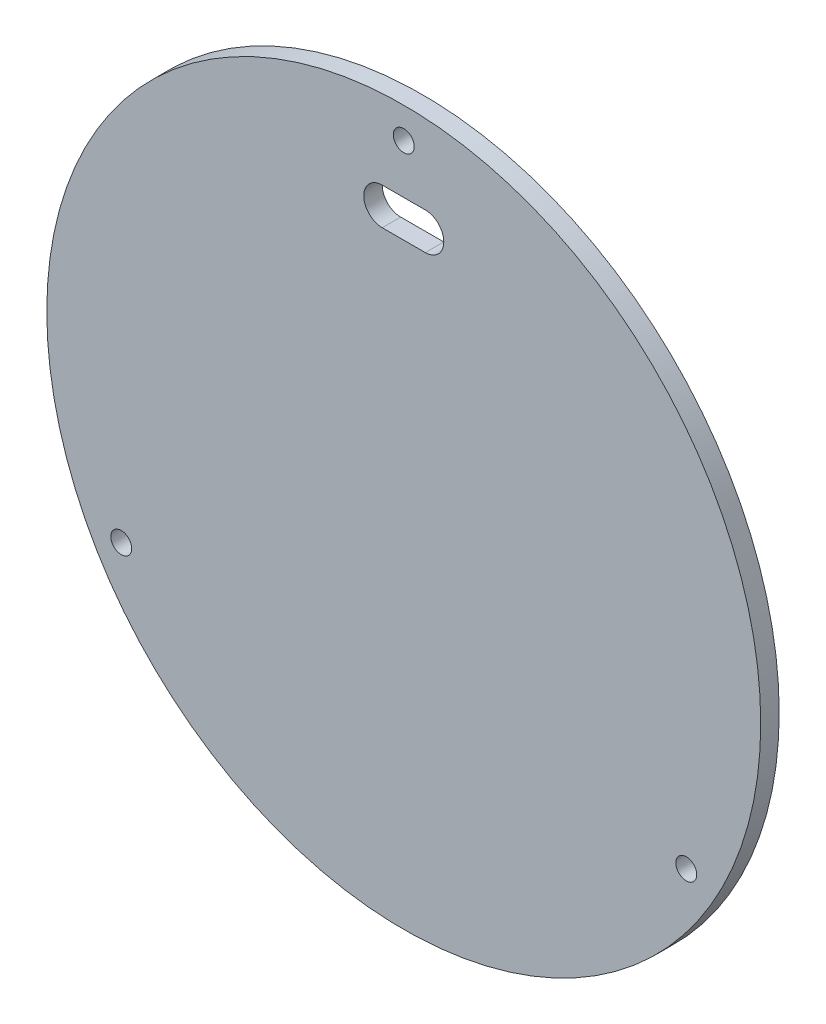
SolidWorks part; units mm, degrees
ref_plane "Front Plane" through (0, 0, 0) normal (0, 0, 1) x (1, 0, 0)
ref_plane "Top Plane" through (0, 0, 0) normal (0, 1, 0) x (1, 0, 0)
ref_plane "Right Plane" through (0, 0, 0) normal (1, 0, 0) x (0, 0, -1)
sketch "Sketch1" plane through (0, 0, 0) normal (0, 0, 1) x (1, 0, 0)
  circle A0 centre (0, 0) radius 58
  circle A1 centre (0, 0) radius 53 construction
  circle A2 centre (0, 53) radius 1.7
  circle A3 centre (45.8993, -26.5) radius 1.7
  circle A4 centre (-45.8993, -26.5) radius 1.7
  point P13 (0, 0)
  dimension "D1" = 116
  dimension "D2" = 106
  dimension "D3" = 3.4
  dimension "D4" = 3
extrude "Boss-Extrude1" add sketch "Sketch1" along normal blind 3
sketch "Sketch2" plane through (0, 0, 3) normal (0, 0, 1) x (1, 0, 0)
  line L0 (-3.5, 42) -> (3.5, 42) construction
  line L1 (-3.5, 45) -> (3.5, 45)
  line L2 (-3.5, 39) -> (3.5, 39)
  arc A5 (-3.5, 45) -> (-3.5, 39) centre (-3.5, 42) ccw
  arc A6 (3.5, 39) -> (3.5, 45) centre (3.5, 42) ccw
  point P3 (0, 42)
  dimension "D1" = 7
  dimension "D2" = 3
  dimension "D3" = 42
extrude "Cut-Extrude1" cut sketch "Sketch2" against normal through all contours L2 A6 L1 A5
